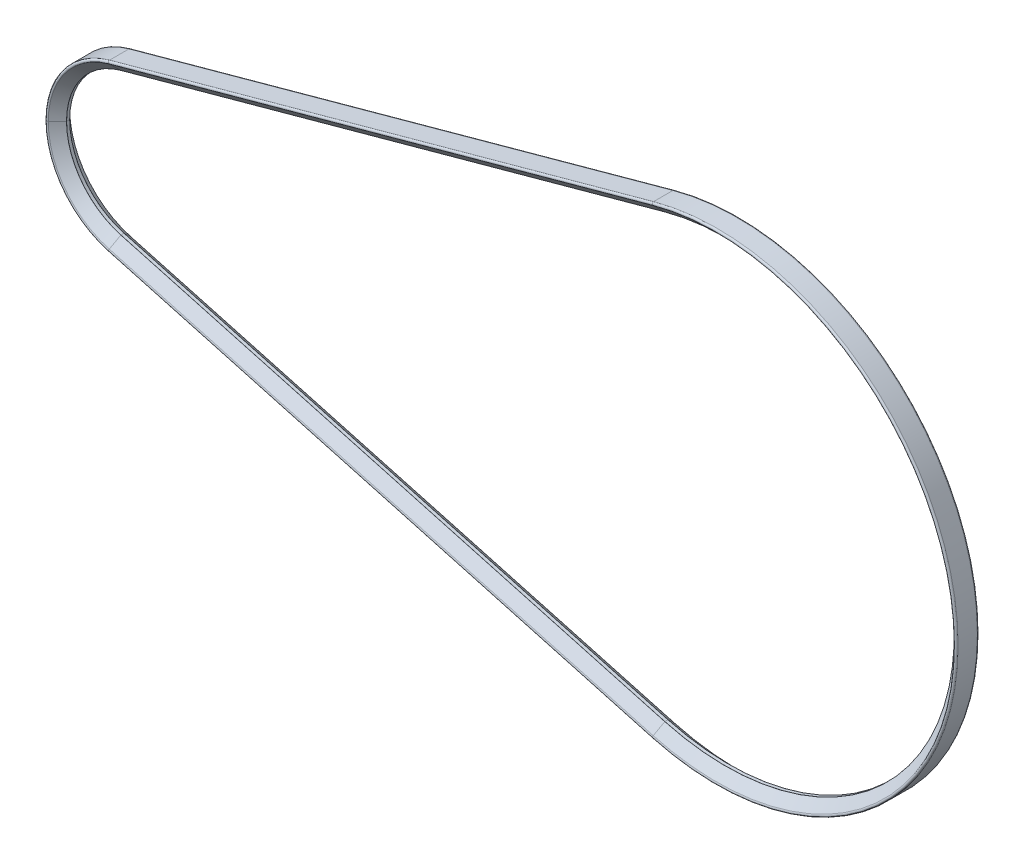
SolidWorks part; units mm, degrees
ref_plane "Front Plane" through (0, 0, 0) normal (0, 0, 1) x (1, 0, 0)
ref_plane "Top Plane" through (0, 0, 0) normal (0, 1, 0) x (1, 0, 0)
ref_plane "Right Plane" through (0, 0, 0) normal (1, 0, 0) x (0, 0, -1)
sketch "Sketch2" plane through (0, 0, 0) normal (0, 0, 1) x (1, 0, 0)
  line L0 (0, 0) -> (1, 0) construction
  line L1 (0, 0) -> (0, 1) construction
  line L2 (-38.2382, 4.508) -> (-3.8339, 13.958)
  line L3 (-3.8339, -13.958) -> (-38.2382, -4.508)
  arc A0 (-38.2382, -4.508) -> (-38.2382, 4.508) centre (-37, 0) cw
  arc A1 (-3.8339, 13.958) -> (-3.8339, -13.958) centre (0, 0) cw
sketch "Sketch3" plane through (0, 0, 0) normal (0, 1, 0) x (1, 0, 0)
  line L0 (-42.425, 0.85) -> (-42.425, -0.85)
  line L1 (-42.425, -0.85) -> (-41.675, -0.1)
  line L2 (-41.675, -0.1) -> (-41.675, 0.1)
  line L3 (-41.675, 0.1) -> (-42.425, 0.85)
  line L4 (-49.1411, 0) -> (-41.675, 0) construction
  line L6 (-41.675, 0) -> (-38.2382, 0) construction
  dimension "D1" = 45
  dimension "D2" = 1.7
  dimension "D3" = 0.75
sweep "Sweep1" add profiles "Sketch3" path "Sketch2"
fillet "Fillet1" radius 0.1 10 edges at (-41.3143, 3.289, -0.85) (-41.3143, -3.289, -0.85) (-21.2347, -9.9562, -0.85) (15.225, 0, -0.85) (-41.3143, 3.289, 0.85) (-41.3143, -3.289, 0.85) (-21.2347, -9.9562, 0.85) (15.225, 0, 0.85) (-21.2347, 9.9562, -0.85) (-21.2347, 9.9562, 0.85)
fillet "Fillet2" radius 0.01 10 edges at (14.475, 0, -0.1) (-21.0361, 9.233, -0.1) (-40.7178, 2.8343, -0.1) (-40.7178, -2.8343, -0.1) (14.475, 0, 0.1) (-21.0361, 9.233, 0.1) (-40.7178, 2.8343, 0.1) (-40.7178, -2.8343, 0.1) (-21.0361, -9.233, -0.1) (-21.0361, -9.233, 0.1)
